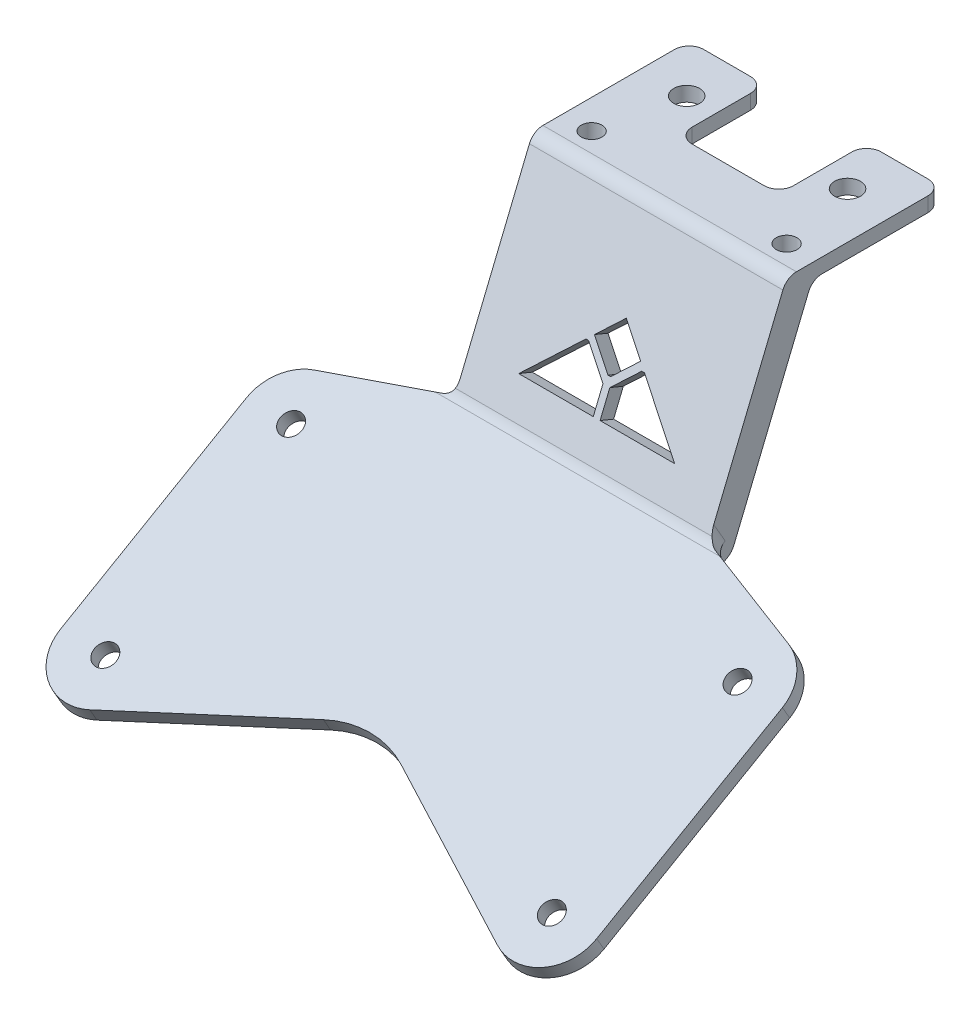
SolidWorks part; units mm, degrees
ref_plane "Front Plane" through (0, 0, 0) normal (0, 0, 1) x (1, 0, 0)
ref_plane "Top Plane" through (0, 0, 0) normal (0, 1, 0) x (1, 0, 0)
ref_plane "Right Plane" through (0, 0, 0) normal (1, 0, 0) x (0, 0, -1)
sketch "Sketch1" plane through (0, 0, 0) normal (0, 1, 0) x (1, 0, 0)
  line L0 (-26.1937, 9.525) -> (26.1937, 9.525) construction
  line L1 (41.275, -25.4) -> (-41.275, -25.4)
  line L2 (41.275, -25.4) -> (41.275, 25.4)
  line L3 (41.275, 25.4) -> (16.51, 25.4)
  line L4 (-41.275, -25.4) -> (-41.275, 25.4)
  line L5 (41.275, -25.4) -> (-41.275, 25.4) construction
  line L6 (41.275, 25.4) -> (-41.275, -25.4) construction
  line L7 (0, 9.525) -> (0, -15.875) construction
  line L8 (-31.75, -15.875) -> (31.75, -15.875) construction
  line L9 (-16.51, 25.4) -> (-16.51, -3.175)
  line L10 (-16.51, -3.175) -> (16.51, -3.175)
  line L11 (16.51, -3.175) -> (16.51, 25.4)
  line L12 (-16.51, 25.4) -> (-41.275, 25.4)
  point P0 (0, 0)
  point P16 (0, -3.175)
  dimension "D1" = 82.55
  dimension "D2" = 50.8
  dimension "D3" = 9.525
  dimension "D4" = 25.4
  dimension "D5" = 63.5
  dimension "D6" = 52.3875
  dimension "D7" = 3.175
  dimension "D8" = 33.02
extrude "Boss-Extrude1" add sketch "Sketch1" along normal blind 4.7625
sketch "Sketch6" plane through (0, 0, 0) normal (1, 0, 0) x (0, 0, -1)
  line L0 (-22.2061, 0) -> (-47.0109, -60.4616)
  line L2 (-25.4, 4.7625) -> (-50.8, -57.15)
  line L3 (-50.8, -57.15) -> (-61.7985, -63.5)
  line L4 (-61.7985, -63.5) -> (-59.4173, -67.6244)
  line L5 (-59.4173, -67.6244) -> (-47.0109, -60.4616)
  line L8 (-22.2061, 0) -> (-26.6123, 1.8076) construction
  line L9 (-25.4, 0) -> (25.4, 0) construction
  line L10 (-22.2061, 0) -> (-25.4, 0)
  line L11 (-25.4, 0) -> (-25.4, 4.7625)
  line L12 (-50.8, -57.15) -> (-50.8, -46.4912) construction
  point P2 (-64.8455, -70.7585)
  dimension "D1" = 4.7625
  dimension "D2" = 50.8
  dimension "D3" = 57.15
  dimension "D4" = 120
  dimension "D5" = 12.7
extrude "Boss-Extrude2" add sketch "Sketch6" along normal mid plane 82.55
sketch "Sketch10" plane through (0, 0, 0) normal (1, 0, 0) x (0, 0, -1)
  line L2 (-17.0584, 0) -> (-43.2218, -63.7733)
  line L3 (-43.2218, -63.7733) -> (-79.0331, -84.4489)
  line L4 (-79.0331, -84.4489) -> (-81.4143, -80.3244)
  line L5 (-81.4143, -80.3244) -> (-47.0109, -60.4616)
  line L6 (-47.0109, -60.4616) -> (-22.2061, 0)
  line L7 (-22.2061, 0) -> (-17.0584, 0)
  line L8 (-22.2061, 0) -> (25.4, 0) construction
  line L9 (-59.4173, -67.6244) -> (-47.0109, -60.4616) construction
  line L10 (-61.7985, -63.5) -> (-59.4173, -67.6244) construction
  point P0 (-70.9343, -83.1254)
  point P1 (-16.5253, 0)
  point P12 (-43.5394, -72.9125)
  point P14 (-55.3774, -74.6217)
  dimension "D1" = 4.7625
  dimension "D2" = 4.7625
  dimension "D3" = 25.4
extrude "Boss-Extrude4" add sketch "Sketch10" against normal blind 4.7625 from surface starting at face at (41.275, -29.9014, 26.9791)
extrude "Boss-Extrude5" add sketch "Sketch10<2>" along normal blind 4.7625 from surface starting at face at (-41.275, -29.9014, 26.9791)
sketch "Sketch10<2>" plane through (0, 0, 0) normal (1, 0, 0) x (0, 0, -1) same geometry as "Sketch10"
sketch "Sketch7" plane through (0, -20.8655, -12.0467) normal (0, 0.866, 0.5) x (1, 0, 0)
  line L0 (-72.7075, -97.9691) -> (72.7075, -97.9691) construction
  line L9 (72.7075, -97.9691) -> (72.7075, -167.8191) construction
  line L14 (72.7075, -167.8191) -> (-72.7075, -167.8191) construction
  line L15 (-72.7075, -167.8191) -> (-72.7075, -97.9691) construction
  line L16 (0, -97.9691) -> (0, -85.2691) construction
  line L17 (41.275, -85.2691) -> (-41.275, -85.2691) construction
  line L18 (-87.3125, -167.8191) -> (-87.3125, -97.9691)
  line L19 (87.3125, -167.8191) -> (87.3125, -97.9691)
  line L20 (41.275, -72.5691) -> (77.1612, -84.0597)
  line L21 (-41.275, -72.5691) -> (-77.1612, -84.0597)
  line L22 (-72.7075, -167.8191) -> (72.7075, -97.9691) construction
  line L23 (72.7075, -167.8191) -> (-72.7075, -97.9691) construction
  line L24 (0, -149.0967) -> (-66.3837, -180.984)
  line L25 (0, -149.0967) -> (66.3837, -180.984)
  line L26 (-41.275, -72.5691) -> (41.275, -72.5691)
  arc A4 (66.3837, -180.984) -> (87.3125, -167.8191) centre (72.7075, -167.8191) ccw
  arc A5 (-87.3125, -167.8191) -> (-66.3837, -180.984) centre (-72.7075, -167.8191) ccw
  arc A6 (-77.1612, -84.0597) -> (-87.3125, -97.9691) centre (-72.7075, -97.9691) ccw
  arc A7 (87.3125, -97.9691) -> (77.1612, -84.0597) centre (72.7075, -97.9691) ccw
  dimension "D3" = 29.21
  dimension "D1" = 145.415
  dimension "D2" = 69.85
  dimension "D4" = 12.7
extrude "Boss-Extrude3" add sketch "Sketch7" against normal blind 4.7625
sketch "Sketch11" plane through (0, 9.6054, 23.4132) normal (0, 0.3796, 0.9252) x (1, 0, 0)
  line L0 (-196.711, 179.457) -> (1087.289, 179.457) construction
  line L1 (-25.4, -59.4548) -> (-9.525, -43.5798)
  line L2 (-9.525, -43.5798) -> (-8.6571, -43.5798)
  line L3 (-8.6571, -43.5798) -> (-1.1112, -51.1257)
  line L4 (-1.1112, -51.1257) -> (-1.1112, -59.4548)
  line L5 (-1.1112, -59.4548) -> (-25.4, -59.4548)
  line L6 (1.1112, -59.4548) -> (25.4, -59.4548)
  line L7 (25.4, -59.4548) -> (9.525, -43.5798)
  line L8 (9.525, -43.5798) -> (8.6571, -43.5798)
  line L9 (8.6571, -43.5798) -> (1.1112, -51.1257)
  line L10 (1.1112, -51.1257) -> (1.1112, -59.4548)
  line L12 (0.434, -48.6598) -> (7.5195, -41.5743)
  line L13 (7.5195, -41.5743) -> (0, -34.0548)
  line L14 (0, -34.0548) -> (-7.5195, -41.5743)
  line L15 (-7.5195, -41.5743) -> (-0.434, -48.6598)
  line L16 (-1.1112, -59.4548) -> (1.1112, -59.4548) construction
  line L17 (275.8352, 377.2606) -> (1559.8352, 377.2606) construction
  line L18 (271.4801, 376.3376) -> (1555.4801, 376.3376) construction
  line L19 (-0.434, -48.6598) -> (0.434, -48.6598)
  line L20 (0, -34.0548) -> (0, -59.4548) construction
  line L21 (41.275, -72.1548) -> (-41.275, -72.1548) construction
  point P10 (21.7153, -46.8164)
  point P13 (26.036, -48.3776)
  point P17 (2.1857, -40.1979)
  point P18 (0, 0)
  point P23 (25.2133, -44.4676)
  dimension "D1" = 25.4
  dimension "D2" = 50.8
  dimension "D3" = 2.2225
  dimension "D4" = 2.2225
  dimension "D5" = 2.2225
  dimension "D6" = 10.795
  dimension "D7" = 15.875
  dimension "D8" = 12.7
extrude "Cut-Extrude1" cut sketch "Sketch11" against normal through all
fillet "Fillet3" radius 4.7625 16 edges at (0, -57.15, 50.8) (-38.8937, -63.7733, 43.2218) (0, -60.4616, 47.0109) (38.8937, -63.7733, 43.2218) (16.51, 2.3813, -25.4) (-16.51, 2.3813, -25.4) (16.51, 2.3813, 3.175) (0, 4.7625, 25.4) (-16.51, 2.3813, 3.175) (0, 0, 22.2061) (-41.275, 2.3813, -25.4) (41.275, 2.3813, -25.4) (38.8937, 0, 17.0584) (-38.8937, 0, 17.0584) (-41.275, -59.2122, 49.6094) (41.275, -59.2122, 49.6094)
fillet "Fillet5" radius 29.21 1 edges at (0, -97.476, 115.8842)
hole_wizard "1/4 Clearance Hole1" positions "Sketch2" profile "Sketch3" hole size "1/4" standard "ANSI Inch" end condition through all
sketch "Sketch2" plane through (0, 4.7625, 0) normal (0, 1, 0) x (1, 0, 0)
  point P0 (-31.75, -15.875)
  point P3 (31.75, -15.875)
sketch "Sketch3" plane through (-31.75, 4.7625, 15.875) normal (1, 0, 0) x (0, 0, 1)
  line L0 (0, 0) -> (0, 120.9644)
  line L1 (0, 120.9644) -> (3.3782, 120.9644)
  line L2 (3.3782, 120.9644) -> (3.3782, 0)
  line L5 (3.3782, 0) -> (0, 0)
  line L11 (0, -6.35) -> (0, 107.95) construction
  dimension "Thru Hole Dia." = 6.7564
  dimension "Thru Hole Depth" = 120.9644
hole_wizard "5/16 Clearance Hole1" positions "Sketch4" profile "Sketch5" hole size "5/16" standard "ANSI Inch" end condition through all
sketch "Sketch4" plane through (0, 4.7625, 0) normal (0, 1, 0) x (1, 0, 0)
  point P0 (-26.1937, 9.525)
  point P3 (26.1937, 9.525)
sketch "Sketch5" plane through (-26.1937, 4.7625, -9.525) normal (1, 0, 0) x (0, 0, 1)
  line L0 (0, 0) -> (0, 120.9644)
  line L1 (0, 120.9644) -> (4.2164, 120.9644)
  line L2 (4.2164, 120.9644) -> (4.2164, 0)
  line L5 (4.2164, 0) -> (0, 0)
  line L11 (0, -6.35) -> (0, 107.95) construction
  dimension "Thru Hole Dia." = 8.4328
  dimension "Thru Hole Depth" = 120.9644
hole_wizard "1/4 Clearance Hole2" positions "Sketch8" profile "Sketch9" hole size "1/4" standard "ANSI Inch" end condition through all
sketch "Sketch8" plane through (0, -20.8655, -12.0467) normal (0, 0.866, 0.5) x (1, 0, 0)
  point P0 (-72.7075, -97.9691)
  point P3 (-72.7075, -167.8191)
  point P6 (72.7075, -167.8191)
  point P9 (72.7075, -97.9691)
sketch "Sketch9" plane through (-72.7075, -69.85, 72.797) normal (1, 0, 0) x (0, -0.5, 0.866)
  line L0 (0, 0) -> (0, 89.2405)
  line L1 (0, 89.2405) -> (3.5712, 89.2405)
  line L2 (3.5712, 89.2405) -> (3.5712, 0)
  line L5 (3.5712, 0) -> (0, 0)
  line L11 (0, -6.35) -> (0, 107.95) construction
  dimension "Thru Hole Dia." = 7.1425
  dimension "Thru Hole Depth" = 89.2405
fillet "Fillet6" radius 2.3812 2 edges at (-38.8937, -84.4489, 79.0331) (38.8937, -84.4489, 79.0331)
equation "\"D2@Sketch10\"=\"D1@Sketch10\""
equation "\"D5@Sketch11\"=\"D3@Sketch11\""
equation "\"D4@Sketch11\"=\"D3@Sketch11\""
